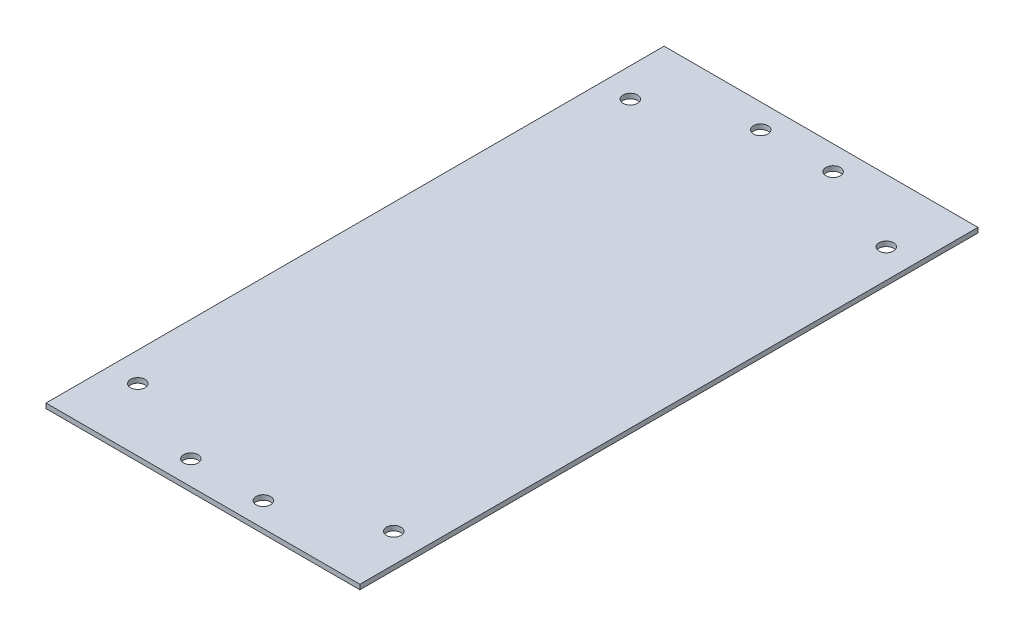
SolidWorks part; units mm, degrees
ref_plane "Спереди" through (0, 0, 0) normal (0, 0, 1) x (1, 0, 0)
ref_plane "Сверху" through (0, 0, 0) normal (0, 1, 0) x (1, 0, 0)
ref_plane "Справа" through (0, 0, 0) normal (1, 0, 0) x (0, 0, -1)
sketch "Эскиз1" plane through (0, 0, 0) normal (0, 1, 0) x (1, 0, 0)
  line L0 (-41.8585, 53.6415) -> (-41.8585, -74.3585) construction
  line L1 (-74.3585, 53.6415) -> (-9.3585, 53.6415)
  line L2 (-74.3585, 53.6415) -> (-74.3585, -74.3585)
  line L3 (-74.3585, -74.3585) -> (-9.3585, -74.3585)
  line L4 (-9.3585, 53.6415) -> (-9.3585, -74.3585)
  line L5 (-74.3585, -10.3585) -> (-9.3585, -10.3585) construction
  circle A0 centre (-68.3585, 40.6415) radius 1.5
  circle A1 centre (-15.3585, 40.6415) radius 1.5
  circle A2 centre (-15.3585, -61.3585) radius 1.5
  circle A3 centre (-68.3585, -61.3585) radius 1.5
  point P0 (0, 0)
  point P12 (-41.8585, -10.3585)
  dimension "D1" = 13
  dimension "D2" = 6
  dimension "D3" = 128
  dimension "D4" = 65
extrude "Бобышка-Вытянуть1" add sketch "Эскиз1" along normal blind 1
sketch "Эскиз2" plane through (0, 1, 0) normal (0, 1, 0) x (1, 0, 0)
  line L0 (-41.8585, 53.6415) -> (-41.8585, -74.3585) construction
  line L1 (-9.3585, 53.6415) -> (-74.3585, 53.6415) construction
  line L2 (-74.3585, -74.3585) -> (-9.3585, -74.3585) construction
  line L3 (-74.3585, -10.3585) -> (-9.3585, -10.3585) construction
  line L4 (-74.3585, 53.6415) -> (-74.3585, -74.3585) construction
  line L5 (-9.3585, -74.3585) -> (-9.3585, 53.6415) construction
  circle A0 centre (-49.3585, 48.6415) radius 1.5
  circle A1 centre (-34.3585, 48.6415) radius 1.5
  circle A2 centre (-34.3585, -69.3585) radius 1.5
  circle A3 centre (-49.3585, -69.3585) radius 1.5
  dimension "D1" = 3
  dimension "D2" = 5
  dimension "D3" = 7.5
extrude "Вырез-Вытянуть1" cut sketch "Эскиз2" against normal through all
